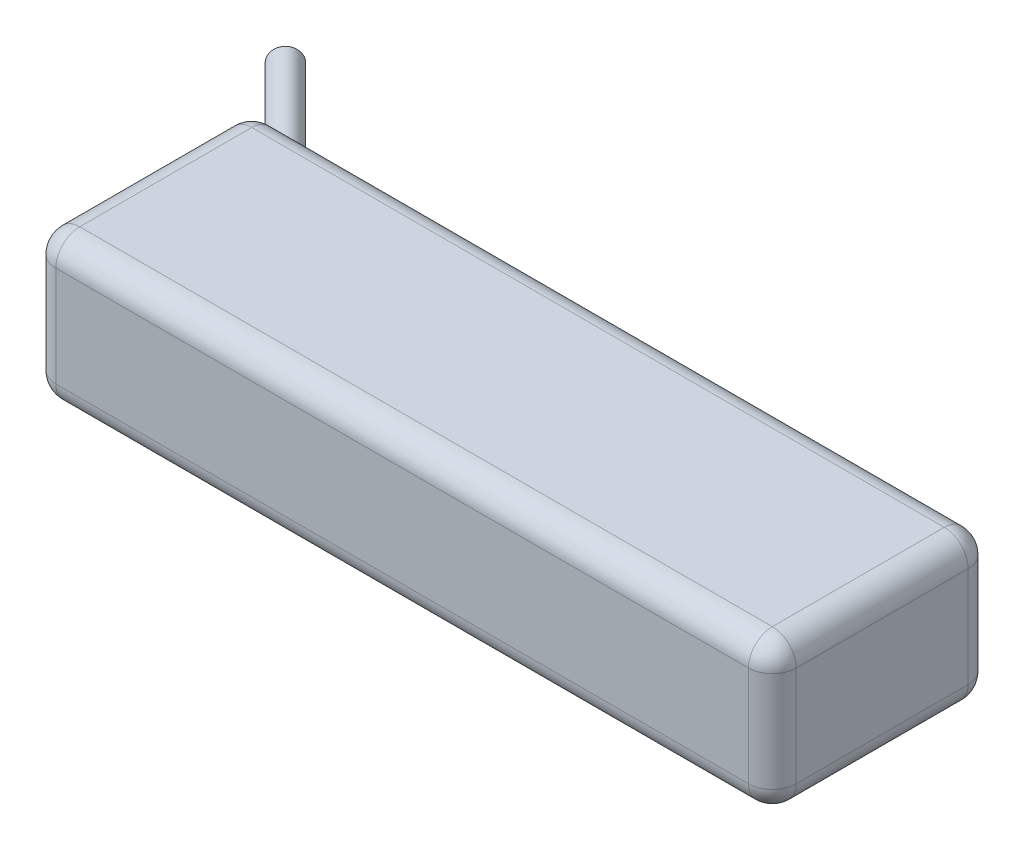
SolidWorks part; units mm, degrees
ref_plane "Front Plane" through (0, 0, 0) normal (0, 0, 1) x (1, 0, 0)
ref_plane "Top Plane" through (0, 0, 0) normal (0, 1, 0) x (1, 0, 0)
ref_plane "Right Plane" through (0, 0, 0) normal (1, 0, 0) x (0, 0, -1)
ref_axis "X" through (-88.99, 0, 0) along (1, 0, 0)
ref_axis "Y" through (0, 55, 0) along (0, -1, 0)
ref_axis "Z" through (0, 0, -88.99) along (0, 0, 1)
sketch "Sketch1" plane through (0, 0, 0) normal (0, 1, 0) x (1, 0, 0)
  line L1 (-77.5, 23) -> (77.5, 23)
  line L2 (-77.5, 23) -> (-77.5, -23)
  line L3 (-77.5, -23) -> (77.5, -23)
  line L4 (77.5, 23) -> (77.5, -23)
  line L5 (-77.5, 23) -> (77.5, -23) construction
  line L6 (-77.5, -23) -> (77.5, 23) construction
  point P0 (0, 0)
  dimension "D1" = 46
  dimension "D2" = 155
extrude "Boss-Extrude1" add sketch "Sketch1" along normal mid plane 31
sketch "Sketch3" plane through (0, 0, 0) normal (0, 1, 0) x (1, 0, 0)
  line L0 (-77.5, 23) -> (-77.5, 13)
  line L1 (-77.5, 13) -> (-67.5, 23)
  line L2 (-67.5, 23) -> (-77.5, 23)
  line L3 (-77.5, 23) -> (-72.5, 18) construction
  dimension "D1" = 45
  dimension "D2" = 10
ref_plane "Plane1" through (-45.25, 0, -45.25) normal (0.7071, 0, 0.7071) x (0.7071, 0, -0.7071)
sketch "Sketch4" plane through (-45.25, 0, -45.25) normal (0.7071, 0, 0.7071) x (0.7071, 0, -0.7071)
  line L0 (-33.5373, 6) -> (-33.5373, -6) construction
  line L1 (0, 0) -> (-33.5373, 0) construction
  line L2 (-38.5373, 15.5) -> (-38.5373, -15.5) construction
  circle A0 centre (-33.5373, 6) radius 3
  circle A1 centre (-33.5373, -6) radius 3
  dimension "D1" = 6
  dimension "D2" = 6
  dimension "D3" = 12
  dimension "D4" = 5
extrude "Boss-Extrude2" add sketch "Sketch4" against normal blind 30
fillet "Fillet1" radius 5 12 edges at (77.5, 0, -23) (-77.5, 0, -23) (-77.5, 0, 23) (77.5, 0, 23) (0, -15.5, -23) (-77.5, -15.5, 0) (0, -15.5, 23) (77.5, -15.5, 0) (0, 15.5, 23) (-77.5, 15.5, 0) (0, 15.5, -23) (77.5, 15.5, 0)
